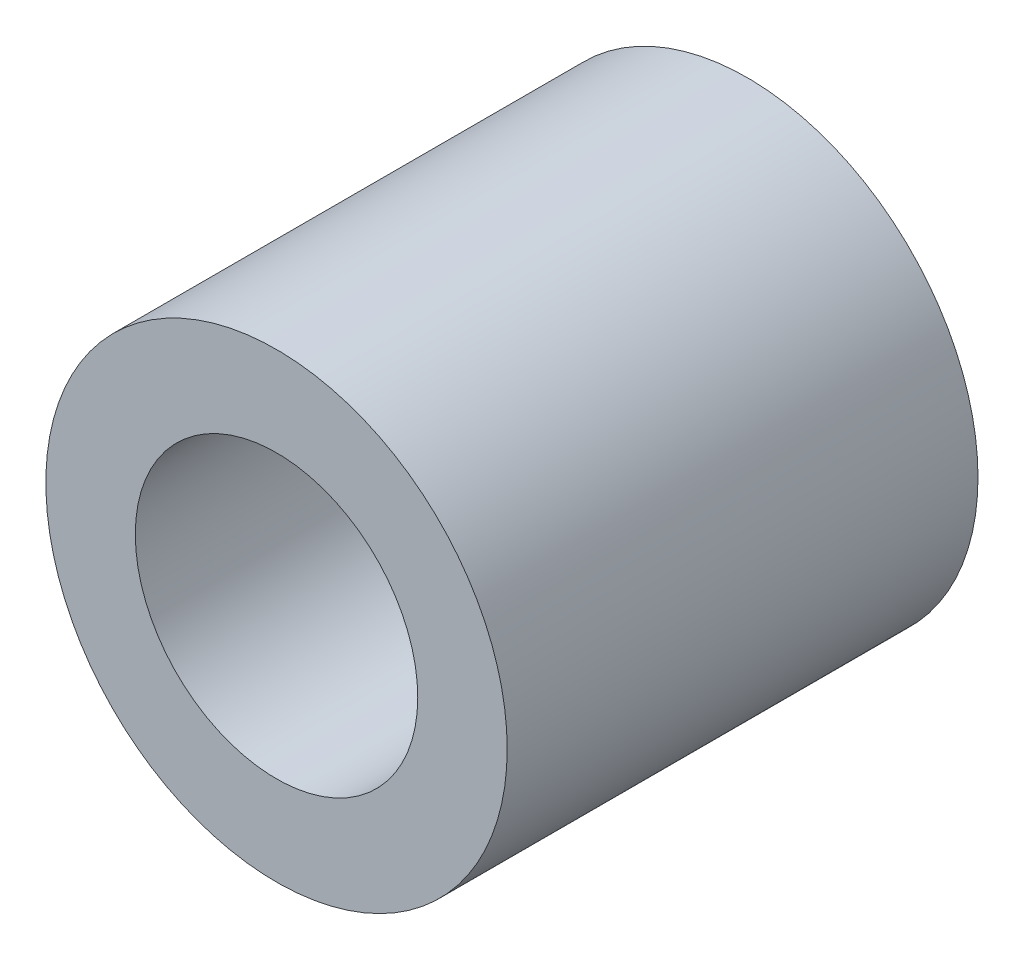
SolidWorks part; units mm, degrees
ref_plane "Front Plane" through (0, 0, 0) normal (0, 0, 1) x (1, 0, 0)
ref_plane "Top Plane" through (0, 0, 0) normal (0, 1, 0) x (1, 0, 0)
ref_plane "Right Plane" through (0, 0, 0) normal (1, 0, 0) x (0, 0, -1)
sketch "Sketch2" plane through (0, 0, 0) normal (0, 0, 1) x (1, 0, 0)
  circle A0 centre (24.4188, 6) radius 4.9
  circle A1 centre (24.4188, 6) radius 1.8
  circle A2 centre (24.4188, 6) radius 3
  dimension "D1" = 9.8
  dimension "D2" = 3.6
  dimension "D3" = 6
extrude "Boss-Extrude1" add sketch "Sketch2" along normal blind 10 contours A0 A2 region at (19.6574, 6, 0)
extrude "Boss-Extrude2" add sketch "Sketch2<3>" along normal blind 3 contours A2 A1 region at (21.5037, 6, 0)
sketch "Sketch2<3>" plane through (0, 0, 0) normal (0, 0, 1) x (1, 0, 0) same geometry as "Sketch2"
